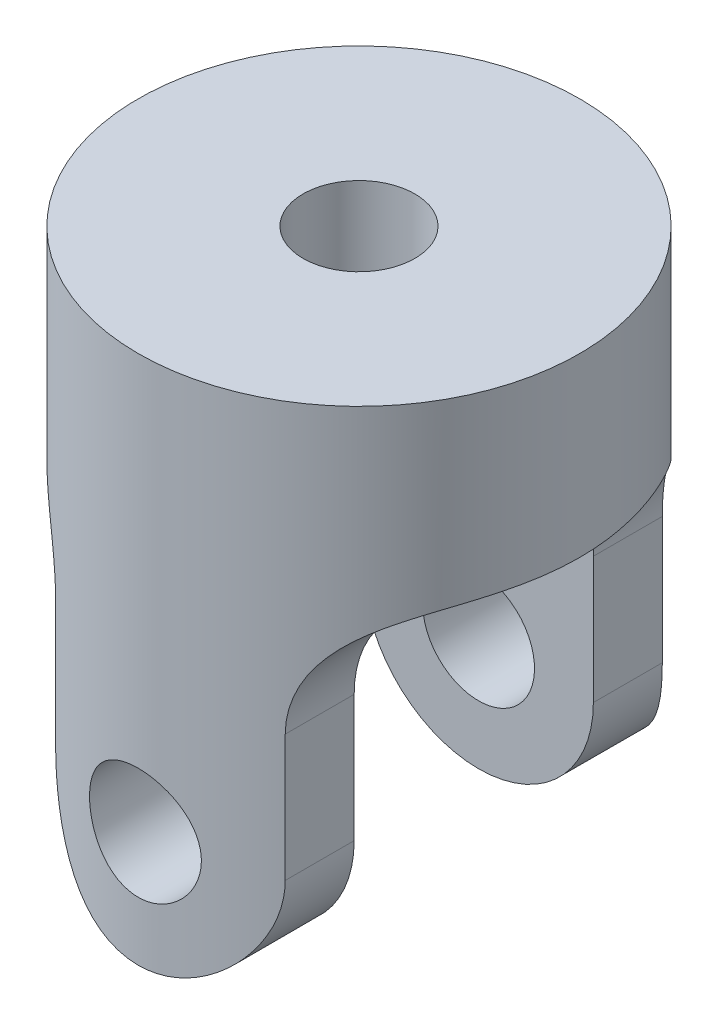
SolidWorks part; units mm, degrees
ref_plane "Front" through (0, 0, 0) normal (0, 0, 1) x (1, 0, 0)
ref_plane "Top" through (0, 0, 0) normal (0, 1, 0) x (-1, 0, 0)
ref_plane "Right" through (0, 0, 0) normal (1, 0, 0) x (0, 0, -1)
sketch "Sketch1" plane through (0, 0, 0) normal (0, 1, 0) x (-1, 0, 0)
  circle A0 centre (0, 0) radius 18.75
  dimension "D1" = 37.5
extrude "Base-Extrude" add sketch "Sketch1" along normal blind 45
sketch "Sketch2" plane through (0, 0, 0) normal (0, 0, 1) x (1, 0, 0)
  line L0 (0, 0) -> (0, 23.7435) construction
  line L1 (9.75, 9.75) -> (9.75, 20.5132)
  line L2 (-9.75, 9.75) -> (-9.75, 20.5132)
  line L3 (18.75, 30) -> (18.75, 0)
  line L4 (-18.75, 45) -> (-18.75, 0) construction
  line L5 (-18.75, 0) -> (-18.75, 30)
  line L6 (18.75, 0) -> (-18.75, 0) construction
  arc A0 (-9.75, 9.75) -> (9.75, 9.75) centre (0, 9.75) ccw
  arc A1 (9.75, 20.5132) -> (18.75, 30) centre (19.25, 20.5132) cw
  arc A2 (-9.75, 20.5132) -> (-18.75, 30) centre (-19.25, 20.5132) ccw
  dimension "D3" = 9.5
  dimension "D2" = 19.5
  dimension "D4" = 30
extrude "Cut-Extrude1" cut sketch "Sketch2" against normal through all and the other way through all flip side to cut
sketch "Sketch8" plane through (0, 0, 0) normal (1, 0, 0) x (0, 0, -1)
  line L0 (-18.75, 0) -> (18.75, 0) construction
  line L1 (-10.16, 0) -> (-10.16, 29.1452)
  line L2 (10.16, 29.1452) -> (-10.16, 29.1452)
  line L3 (10.16, 29.1452) -> (10.16, 0)
  line L4 (0, 0) -> (0, 14.3858) construction
  point P4 (0, 0)
  dimension "D1" = 29.1452
  dimension "D2" = 20.32
extrude "Cut-Extrude5" cut sketch "Sketch8" against normal through all and the other way through all flip side to cut
sketch "Sketch11" plane through (0, 0, 0) normal (0, 0, 1) x (1, 0, 0)
  circle A0 centre (0, 9.75) radius 4.75
  dimension "D1" = 9.5
extrude "Cut-Extrude6" cut sketch "Sketch11" against normal through all and the other way through all
sketch "Sketch12" plane through (0, 45, 0) normal (0, 1, 0) x (-1, 0, 0)
  circle A0 centre (0, 0) radius 4.75
  dimension "D1" = 9.5
extrude "Cut-Extrude7" cut sketch "Sketch12" against normal through all
ref_axis "Axis1" through (0, 95, 0) along (0, -1, 0)
